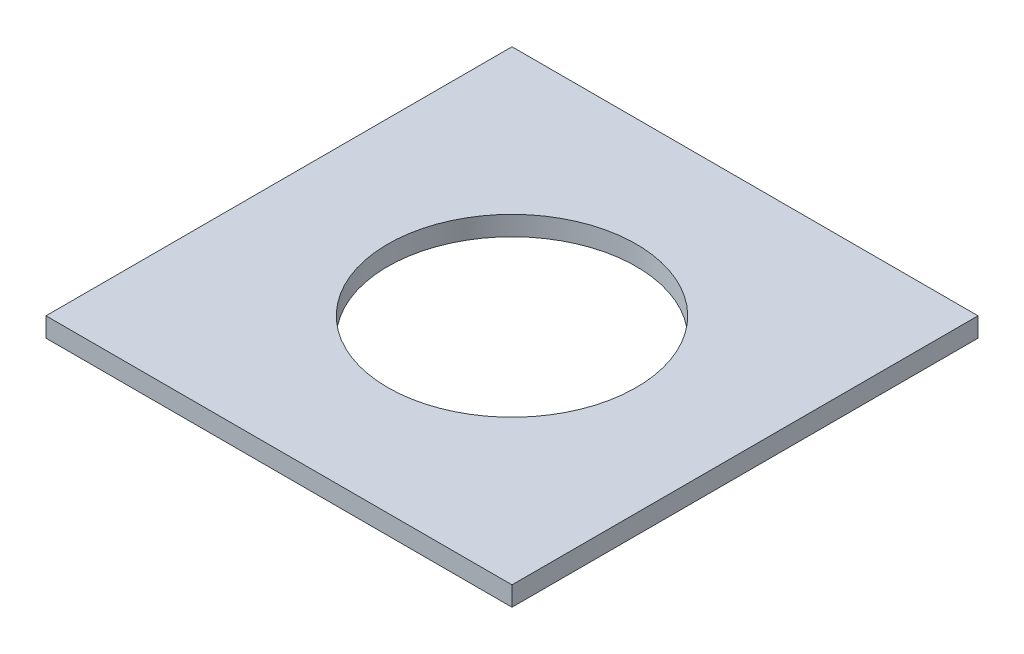
SolidWorks part; units mm, degrees
material "MDF"
ref_plane "Front Plane" through (0, 0, 0) normal (0, 0, 1) x (1, 0, 0)
ref_plane "Top Plane" through (0, 0, 0) normal (0, 1, 0) x (1, 0, 0)
ref_plane "Right Plane" through (0, 0, 0) normal (1, 0, 0) x (0, 0, -1)
sketch "Sketch1" plane through (0, 0, 0) normal (0, 1, 0) x (1, 0, 0)
  line L1 (-152.4, -152.4) -> (152.4, -152.4)
  line L2 (-152.4, -152.4) -> (-152.4, 152.4)
  line L3 (-152.4, 152.4) -> (152.4, 152.4)
  line L4 (152.4, -152.4) -> (152.4, 152.4)
  line L5 (-152.4, -152.4) -> (152.4, 152.4) construction
  line L6 (-152.4, 152.4) -> (152.4, -152.4) construction
  point P0 (0, 0)
  dimension "D1" = 304.8
extrude "Boss-Extrude1" add sketch "Sketch1" along normal blind 12.7
sketch "Sketch5" plane through (0, 12.7, 0) normal (0, 1, 0) x (1, 0, 0)
  circle A0 centre (0, 0) radius 81.2764
  circle A1 centre (0, 0) radius 81.2764
extrude "Cut-Extrude4" cut sketch "Sketch5" against normal through all
